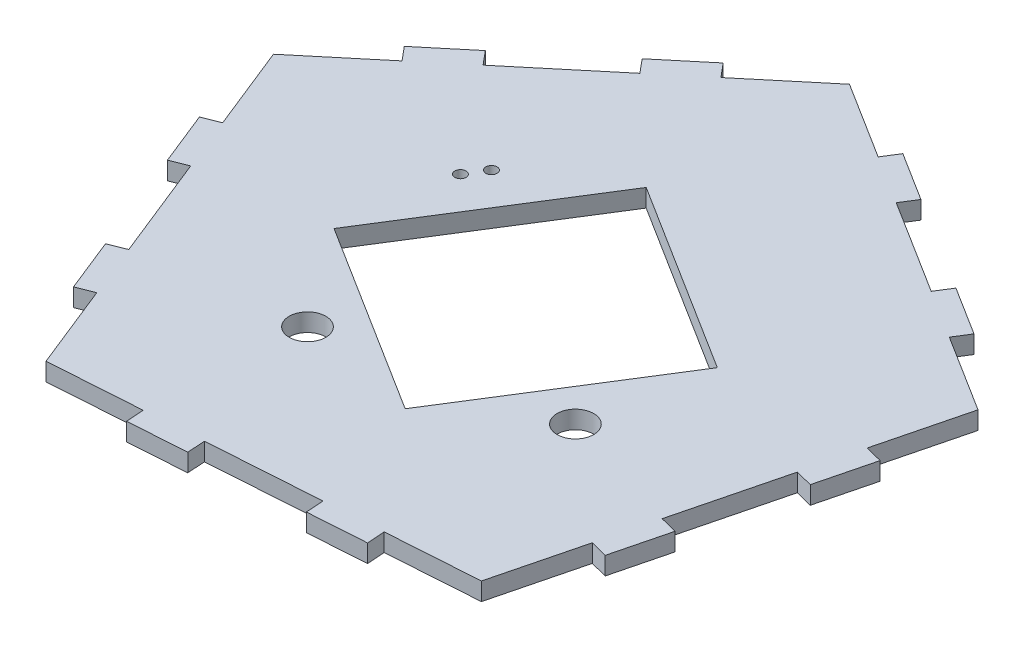
SolidWorks part; units mm, degrees
ref_plane "Front Plane" through (0, 0, 0) normal (0, 0, 1) x (1, 0, 0)
ref_plane "Top Plane" through (0, 0, 0) normal (0, 1, 0) x (1, 0, 0)
ref_plane "Right Plane" through (0, 0, 0) normal (1, 0, 0) x (0, 0, -1)
sketch "Sketch1" plane through (0, 0, 0) normal (0, 1, 0) x (1, 0, 0)
  line L1 (-59.9258, 15.1181) -> (-32.8962, -52.3211)
  line L2 (-32.8962, -52.3211) -> (39.5948, -47.4543)
  line L3 (39.5948, -47.4543) -> (57.3672, 22.9927)
  line L4 (57.3672, 22.9927) -> (-4.14, 61.6646)
  line L5 (-4.14, 61.6646) -> (-59.9258, 15.1181)
  circle A0 centre (0, 0) radius 50 construction
  dimension "D1" = 100
extrude "Boss-Extrude1" add sketch "Sketch1" along normal blind 3.18
ref_axis "Axis" through (0, 3.339, 0) along (0, -1, 0)
sketch "Axis Check" plane through (0, 3.18, 0) normal (0, 1, 0) x (1, 0, 0)
  line L0 (3.3493, -49.8877) -> (-4.14, 61.6646) construction
  line L1 (-32.8962, -52.3211) -> (39.5948, -47.4543) construction
  line L2 (57.3672, 22.9927) -> (-46.411, -18.6015) construction
  line L3 (-59.9258, 15.1181) -> (-32.8962, -52.3211) construction
  line L4 (-32.0329, 38.3913) -> (39.5948, -47.4543) construction
  line L5 (-4.14, 61.6646) -> (-59.9258, 15.1181) construction
  line L6 (-59.9258, 15.1181) -> (48.481, -12.2308) construction
  line L7 (39.5948, -47.4543) -> (57.3672, 22.9927) construction
  line L8 (-32.8962, -52.3211) -> (26.6136, 42.3287) construction
  line L9 (57.3672, 22.9927) -> (-4.14, 61.6646) construction
sketch "Sketch2" plane through (0, 0, 0) normal (0, -1, 0) x (1, 0, 0)
  line L0 (-53.8107, 0.1392) -> (-50.859, -1.0438)
  line L1 (-53.8107, 0.1392) -> (-50.1723, 9.2172)
  line L2 (-50.859, -1.0438) -> (-47.2205, 8.0342)
  line L3 (-50.1723, 9.2172) -> (-47.2205, 8.0342)
  line L4 (-59.9258, -15.1181) -> (-32.8962, 52.3211) construction
  line L5 (-42.6498, 27.9858) -> (-39.0113, 37.0638)
  line L6 (-42.6498, 27.9858) -> (-39.6981, 26.8028)
  line L7 (-39.0113, 37.0638) -> (-36.0596, 35.8808)
  line L8 (-39.6981, 26.8028) -> (-36.0596, 35.8808)
  line L9 (-46.411, 18.6015) -> (-19.2439, 7.7129) construction
  line L10 (-40.8306, 32.5248) -> (-37.8788, 31.3418) construction
  dimension "D1" = 3.18
  dimension "D2" = 9.78
  dimension "D3" = 10.11
extrude "Cut F" [suppressed] cut sketch "Sketch2" against normal through all
sketch "Sketch4" plane through (0, 3.18, 0) normal (0, 1, 0) x (1, 0, 0)
  line L9 (26.6136, 42.3287) -> (-26.6136, -42.3287) construction
  line L10 (57.3672, 22.9927) -> (-4.14, 61.6646) construction
  line L11 (-27.7286, -6.3206) -> (-6.3206, 27.7286)
  line L12 (-27.7286, -6.3206) -> (6.3206, -27.7286)
  line L13 (-6.3206, 27.7286) -> (27.7286, 6.3206)
  line L14 (6.3206, -27.7286) -> (27.7286, 6.3206)
  line L15 (-27.7286, -6.3206) -> (27.7286, 6.3206) construction
  line L16 (-6.3206, 27.7286) -> (6.3206, -27.7286) construction
  line L20 (0, 0) -> (39.0006, -24.5211) construction
  circle A0 centre (-14.9622, -23.7972) radius 3.25
  circle A1 centre (23.7972, -14.9622) radius 3.25
  point P5 (0, 0)
  point P6 (-14.9622, -23.7972)
  point P25 (0, 0)
  point P26 (0, 0)
  point P27 (0, 0)
  point P28 (27.5063, 7.2269)
  point P29 (23.7972, -14.9622)
  dimension "D3" = 6.5
  dimension "D1" = 40.22
  dimension "D2" = 40.22
  dimension "D4" = 8
  dimension "D5" = 8
extrude "Top Cut" cut sketch "Sketch4" against normal blind 10
sketch "Sketch7" plane through (0, 3.18, 0) normal (0, 1, 0) x (1, 0, 0)
  line L0 (0, 0) -> (26.6136, 42.3287) construction
  line L1 (57.3672, 22.9927) -> (-4.14, 61.6646) construction
  line L2 (1.0645, 1.6931) -> (-22.7326, 16.6553) construction
  line L3 (-6.1086, 1.4782) -> (-24.8617, 13.269) construction
  line L5 (-6.3206, 27.7286) -> (-27.7286, -6.3206) construction
  circle A0 centre (-22.7326, 16.6553) radius 1
  circle A1 centre (-24.8617, 13.269) radius 1
  dimension "D5" = 2
  dimension "D1" = 4
  dimension "D2" = 2
  dimension "D3" = 8
  dimension "D4" = 8
extrude "Top Cut 2" cut sketch "Sketch7" against normal through all
sketch "Sketch3" plane through (0, 3.18, 0) normal (0, 1, 0) x (1, 0, 0)
  line L0 (0, 0) -> (-40.9819, 49.1167) construction
  line L1 (-49.5112, 27.9494) -> (-45.4366, 23.066)
  line L3 (-45.4366, 23.066) -> (-37.5894, 29.6135)
  line L4 (-41.664, 34.4969) -> (-37.5894, 29.6135)
  line L5 (-4.14, 61.6646) -> (-59.9258, 15.1181) construction
  line L6 (-71.9961, 5.0469) -> (-69.9588, 2.6052)
  line L7 (-71.9961, 5.0469) -> (-47.4739, 25.5077)
  line L14 (-26.4764, 47.1691) -> (-22.4018, 42.2857)
  line L16 (-22.4018, 42.2857) -> (-14.5546, 48.8333)
  line L17 (-18.6292, 53.7166) -> (-14.5546, 48.8333)
  line L18 (-42.539, 27.5695) -> (-41.513, 26.3398) construction
  line L19 (-49.5112, 27.9494) -> (-41.664, 34.4969)
  line L21 (-26.4764, 47.1691) -> (-18.6292, 53.7166)
  line L22 (-16.5919, 51.275) -> (4.7866, 69.1127)
  line L23 (-39.6267, 32.0552) -> (-24.4391, 44.7274)
  line M18 (-4.14, 61.6646) -> (-59.9258, 15.1181)
  dimension "D1" = 3.18
  dimension "D2" = 10.22
  dimension "D3" = 9.89
  dimension "D4" = 100
extrude "Extrude M" add sketch "Sketch3" against normal up to surface (3.18 mm away) contours L21 L14 L7 L17 | L19 L1 L4 M18 region at (-44.5689, 3.18, -30.0023) region at (-21.5341, 3.18, -49.222) up to face at (-22.7326, 0, -15.6553)
pattern_circular "Circle F" [suppressed] count 5 over 360 about axis through (0, 3.339, 0) along (0, -1, 0) of bodies 173
pattern_circular "Circle M" count 5 over 360 about axis through (0, 3.339, 0) along (0, -1, 0) of "Extrude M"
pattern_circular "Circle Side F" [suppressed] count 5 over 360 about axis through (0, 3.339, 0) along (0, -1, 0) of bodies 173
pattern_circular "Circle Side M" [suppressed] count 5 over 360 about axis through (0, 3.339, 0) along (0, -1, 0) of bodies 168
sketch "Sketch6" [suppressed] plane through (0, 3.18, 0) normal (0, 1, 0) x (1, 0, 0)
  line L0 (49.2535, -57.226) -> (49.2535, 42.774) construction
  line L1 (-50.7465, -57.226) -> (49.2535, -57.226) construction
  line L2 (19.2535, -27.226) -> (19.2535, 21.074) construction
  circle A0 centre (-33.1465, 5.774) radius 1.6
  circle A1 centre (-33.1465, -22.126) radius 1.6
  circle A2 centre (17.6535, 21.074) radius 1.6
  circle A3 centre (19.2535, -27.226) radius 1.6
  dimension "D1" = 3.2
  dimension "D2" = 50.8
  dimension "D3" = 27.9
  dimension "D7" = 5.1
  dimension "D4" = 48.3
  dimension "D5" = 30
  dimension "D6" = 30
equation "\"kerf\"= .22mm"
equation "\"tabWidthF\"= 10 - \"kerf\""
equation "\"tabThickness\"= 3.18"
equation "\"D1@Sketch2\"=\"tabThickness\""
equation "\"tabWidthM\"= 10 + \"kerf\""
equation "\"halfkerf\"= \"kerf\" / 2.00mm"
equation "\"tabLength\" = \"kerf\" + 12"
